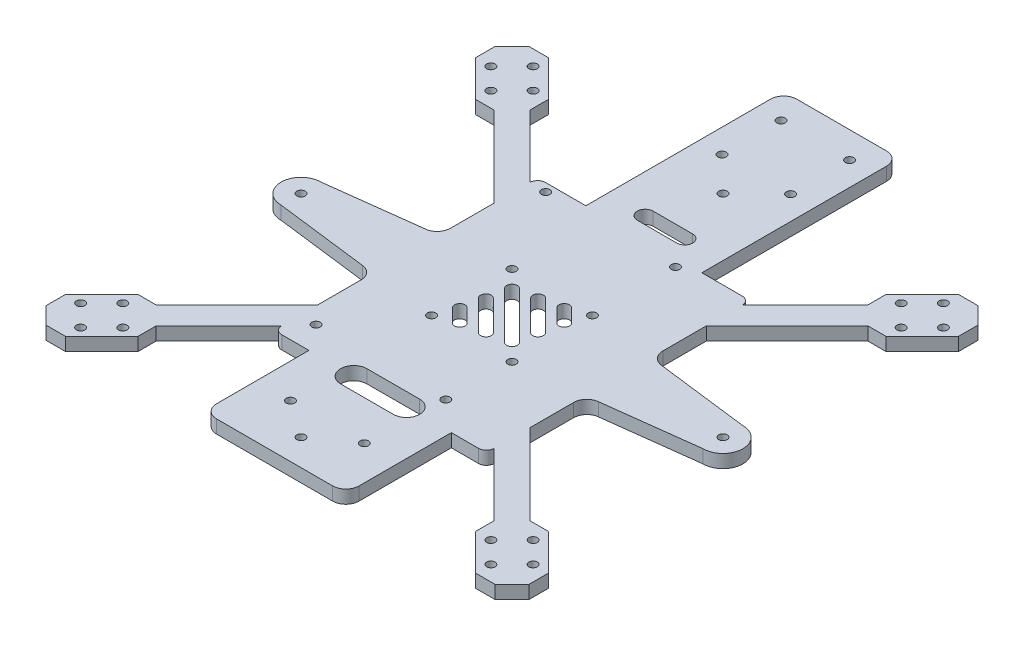
SolidWorks part; units mm, degrees
material "3k碳纤维板"
ref_plane "前视基准面" through (0, 0, 0) normal (0, 0, 1) x (1, 0, 0)
ref_plane "上视基准面" through (0, 0, 0) normal (0, 1, 0) x (1, 0, 0)
ref_plane "右视基准面" through (0, 0, 0) normal (1, 0, 0) x (0, 0, -1)
other "Configuration Table"
sketch "草图1" plane through (0, 0, 0) normal (0, 1, 0) x (1, 0, 0)
  line L0 (-40.28, 0) -> (40.28, 0) construction
  line L1 (-40.28, -50) -> (40.28, -50)
  line L2 (-40.28, -50) -> (-40.28, -16.9164)
  line L3 (-40.28, 50) -> (40.28, 50)
  line L4 (40.28, -50) -> (40.28, -16.9164)
  line L5 (-40.28, -50) -> (40.28, 50) construction
  line L6 (-40.28, 50) -> (40.28, -50) construction
  line L7 (0, -50) -> (0, 50) construction
  line L8 (-40.28, -50) -> (-40.28, -90) construction
  line L9 (-40.28, -90) -> (40.28, -90) construction
  line L10 (40.28, -90) -> (40.28, -50) construction
  line L11 (0, -50) -> (0, -90) construction
  line L12 (-40.28, -70) -> (40.28, -70) construction
  line L13 (-27, -90) -> (27, -90)
  line L14 (27, -90) -> (27, -50)
  line L15 (-27, -90) -> (-27, -50)
  line L16 (44.6626, 11.9547) -> (80, 7.5578)
  line L17 (44.6626, -11.9547) -> (80, -7.5578)
  line L18 (-44.6626, -11.9547) -> (-80, -7.5578)
  line L19 (-44.6626, 11.9547) -> (-80, 7.5578)
  line L20 (40.28, 16.9164) -> (40.28, 50)
  line L21 (-40.28, 16.9164) -> (-40.28, 50)
  circle A0 centre (-34.12, 46.89) radius 1.6
  circle A1 centre (15.09, 46.89) radius 1.6
  circle A2 centre (15.09, -40.19) radius 1.6
  circle A3 centre (-34.12, -40.19) radius 1.6
  circle A5 centre (-15.25, 15.25) radius 1.6
  circle A6 centre (15.25, 15.25) radius 1.6
  circle A7 centre (15.25, -15.25) radius 1.6
  circle A8 centre (-15.25, -15.25) radius 1.6
  circle A9 centre (14, -70) radius 1.6
  circle A10 centre (-14, -70) radius 1.6
  circle A11 centre (80, 0) radius 7.5 construction
  circle A12 centre (-80, 0) radius 7.5 construction
  circle A14 centre (80, 0) radius 1.6
  circle A16 centre (-80, 0) radius 1.6
  arc A17 (80, 7.5578) -> (80, -7.5578) centre (80, 0) cw
  arc A18 (-80, 7.5578) -> (-80, -7.5578) centre (-80, 0) ccw
  arc A19 (44.6626, 11.9547) -> (40.28, 16.9164) centre (45.28, 16.9164) cw
  arc A20 (44.6626, -11.9547) -> (40.28, -16.9164) centre (45.28, -16.9164) ccw
  arc A21 (-44.6626, -11.9547) -> (-40.28, -16.9164) centre (-45.28, -16.9164) cw
  arc A22 (-44.6626, 11.9547) -> (-40.28, 16.9164) centre (-45.28, 16.9164) ccw
  point P0 (0, 0)
  point P19 (0, 0)
  point P22 (0, 0)
  point P40 (0, -90)
  point P62 (40.28, 12.5)
  point P65 (40.28, -12.5)
  point P68 (-40.28, -12.5)
  point P71 (-40.28, 12.5)
  dimension "D3" = 3.2
  dimension "D10" = 3.2
  dimension "D11" = 30.5
  dimension "D12" = 30.5
  dimension "D14" = 3.2
  dimension "D18" = 15
  dimension "D21" = 3.2
  dimension "D19" = 160
  dimension "D23" = 5
  dimension "D1" = 80.56
  dimension "D2" = 100
  dimension "D4" = 6.16
  dimension "D5" = 3.11
  dimension "D8" = 49.21
  dimension "D9" = 87.08
  dimension "D13" = 40
  dimension "D15" = 28
  dimension "D16" = 54
  dimension "D17" = 25
  dimension "D6" = 2
  dimension "D7" = 2
extrude "凸台-拉伸1" add sketch "草图1" along normal blind 5 contours L15 L13 L14 L1 A9 A10 | L1 L4 L3 L2 A6 A5 A3 A2 A1 A0 A7 A8 region at (0.0313, 0, 0.011) region at (0, 0, 70)
sketch "草图6" plane through (0, 0, 0) normal (0, 1, 0) x (1, 0, 0)
  line L0 (0, 0) -> (50000, 0) construction
  line L1 (0, 0) -> (0, 50000) construction
  line L2 (-77.7817, 77.7817) -> (77.7817, 77.7817) construction
  line L3 (77.7817, 77.7817) -> (77.7817, -77.7817) construction
  line L4 (69.7817, 77.7817) -> (85.7817, 77.7817) construction
  line L5 (77.7817, 69.7817) -> (77.7817, 85.7817) construction
  line L6 (-77.7817, -77.7817) -> (77.7817, 77.7817) construction
  line L7 (77.7817, 91.5317) -> (64.0317, 77.7817)
  line L8 (91.5317, 77.7817) -> (77.7817, 64.0317)
  line L9 (-70.9067, 64.0317) -> (-40.28, 33.405)
  line L10 (-91.5317, -91.5317) -> (88.3498, 88.3498) construction
  line L11 (-87.5951, 87.5951) -> (77.7817, -77.7817) construction
  line L12 (40.28, -50) -> (40.28, 50)
  line L13 (40.28, 50) -> (-40.28, 50)
  line L14 (-40.28, 50) -> (-40.28, -50)
  line L15 (-40.28, -50) -> (40.28, -50)
  line L16 (-77.7817, 64.0317) -> (-70.9067, 64.0317)
  line L17 (-91.5317, 77.7817) -> (-77.7817, 64.0317)
  line L18 (-91.5317, 77.7817) -> (-91.5317, 85.1678)
  line L19 (-85.1678, 91.5317) -> (-91.5317, 85.1678)
  line L20 (-77.7817, 91.5317) -> (-85.1678, 91.5317)
  line L21 (77.7817, 91.5317) -> (85.1678, 91.5317)
  line L22 (91.5317, 77.7817) -> (91.5317, 85.1678)
  line L23 (-77.7817, 91.5317) -> (-64.0317, 77.7817)
  line L24 (-64.0317, 77.7817) -> (-64.0317, 70.9067)
  line L25 (72.1249, 83.4386) -> (83.4386, 72.1249) construction
  line L26 (77.7817, 64.0317) -> (70.9067, 64.0317)
  line L27 (64.0317, 77.7817) -> (64.0317, 70.9067)
  line L28 (77.7817, 64.0317) -> (70.9067, 64.0317)
  line L29 (64.0317, 77.7817) -> (64.0317, 70.9067)
  line L30 (64.0317, 70.9067) -> (40.28, 47.155)
  line L31 (70.9067, 64.0317) -> (40.28, 33.405)
  line L32 (85.1678, 91.5317) -> (91.5317, 85.1678)
  line L33 (-64.0317, 70.9067) -> (-40.28, 47.155)
  line L34 (-64.0317, -70.9067) -> (-40.28, -47.155)
  line L35 (-64.0317, -77.7817) -> (-64.0317, -70.9067)
  line L36 (-77.7817, -91.5317) -> (-64.0317, -77.7817)
  line L37 (-77.7817, -91.5317) -> (-85.1678, -91.5317)
  line L38 (-85.1678, -91.5317) -> (-91.5317, -85.1678)
  line L39 (-91.5317, -77.7817) -> (-91.5317, -85.1678)
  line L40 (-91.5317, -77.7817) -> (-77.7817, -64.0317)
  line L41 (-77.7817, -64.0317) -> (-70.9067, -64.0317)
  line L42 (-70.9067, -64.0317) -> (-40.28, -33.405)
  line L43 (70.9067, -64.0317) -> (40.28, -33.405)
  line L44 (77.7817, -64.0317) -> (70.9067, -64.0317)
  line L45 (91.5317, -77.7817) -> (77.7817, -64.0317)
  line L46 (91.5317, -77.7817) -> (91.5317, -85.1678)
  line L47 (85.1678, -91.5317) -> (91.5317, -85.1678)
  line L48 (77.7817, -91.5317) -> (85.1678, -91.5317)
  line L49 (77.7817, -91.5317) -> (64.0317, -77.7817)
  line L50 (64.0317, -77.7817) -> (64.0317, -70.9067)
  line L51 (64.0317, -70.9067) -> (40.28, -47.155)
  circle A0 centre (-77.7817, 77.7817) radius 65.9 construction
  circle A1 centre (77.7817, 77.7817) radius 65.9 construction
  circle A2 centre (-77.7817, -77.7817) radius 65.9 construction
  circle A3 centre (77.7817, -77.7817) radius 65.9 construction
  circle A4 centre (0, 0) radius 110 construction
  circle A5 centre (77.7817, 77.7817) radius 8 construction
  circle A6 centre (77.7817, 85.7817) radius 1.6
  circle A7 centre (85.7817, 77.7817) radius 1.6
  circle A8 centre (77.7817, 69.7817) radius 1.6
  circle A9 centre (69.7817, 77.7817) radius 1.6
  circle A10 centre (77.7817, 77.7817) radius 13.75 construction
  circle A11 centre (-77.7817, 85.7817) radius 1.6
  circle A12 centre (-85.7817, 77.7817) radius 1.6
  circle A13 centre (-69.7817, 77.7817) radius 1.6
  circle A14 centre (-77.7817, 69.7817) radius 1.6
  circle A15 centre (-77.7817, -69.7817) radius 1.6
  circle A16 centre (-69.7817, -77.7817) radius 1.6
  circle A17 centre (-85.7817, -77.7817) radius 1.6
  circle A18 centre (-77.7817, -85.7817) radius 1.6
  circle A19 centre (77.7817, -85.7817) radius 1.6
  circle A20 centre (85.7817, -77.7817) radius 1.6
  circle A21 centre (69.7817, -77.7817) radius 1.6
  circle A22 centre (77.7817, -69.7817) radius 1.6
  point P18 (77.7817, 77.7817)
  point P21 (77.7817, 77.7817)
  point P24 (0, 0)
  point P31 (77.7817, 77.7817)
  point P77 (77.7817, 77.7817)
  dimension "D1" = 3.2
  dimension "D2" = 3.2
  dimension "D3" = 3.2
  dimension "D4" = 3.2
  dimension "D5" = 3.2
  dimension "D6" = 3.2
  dimension "D7" = 3.2
  dimension "D8" = 3.2
  dimension "D9" = 3.2
  dimension "D10" = 3.2
  dimension "D11" = 3.2
  dimension "D12" = 3.2
  dimension "D13" = 3.2
  dimension "D14" = 3.2
  dimension "D15" = 3.2
  dimension "D16" = 3.2
extrude "凸台-拉伸3" add sketch "草图6" along normal blind 5 contours L33 L24 L23 L20 L19 L18 L17 L16 L9 L14 A13 A11 A12 A14 | L32 L21 L7 L27 L30 L12 L31 L26 L8 L22 A9 A8 A7 A6 | L51 L50 L49 L48 L47 L46 L45 L44 L43 L12 A21 A19 A20 A22 | L42 L41 L40 L39 L38 L37 L36 L35 L34 L14 A18 A17 A16 A15 region at (67.5211, 0, -67.3959) region at (67.5211, 0, 67.3959) region at (-67.5211, 0, -67.3959) region at (-67.5211, 0, 67.3959)
sketch "草图7" plane through (0, 0, 0) normal (0, 1, 0) x (1, 0, 0)
  line L0 (-8.8388, 8.8388) -> (8.8388, -8.8388) construction
  line L1 (-15.25, -15.25) -> (15.25, -15.25) construction
  line L2 (-15.25, -15.25) -> (-15.25, 15.25) construction
  line L3 (-15.25, 15.25) -> (15.25, 15.25) construction
  line L4 (15.25, -15.25) -> (15.25, 15.25) construction
  line L5 (-15.25, -15.25) -> (15.25, 15.25) construction
  line L6 (-15.25, 15.25) -> (15.25, -15.25) construction
  line L7 (-7.4246, 10.253) -> (10.253, -7.4246)
  line L8 (-10.253, 7.4246) -> (7.4246, -10.253)
  line L9 (-0.7071, 10.6066) -> (10.6066, -0.7071) construction
  line L10 (0.7071, 12.0208) -> (12.0208, 0.7071)
  line L11 (-2.1213, 9.1924) -> (9.1924, -2.1213)
  line L12 (7.4246, 12.3744) -> (12.3744, 7.4246) construction
  line L13 (8.8388, 13.7886) -> (13.7886, 8.8388)
  line L14 (6.0104, 10.9602) -> (10.9602, 6.0104)
  line L15 (-12.3744, -7.4246) -> (-7.4246, -12.3744) construction
  line L16 (-13.7886, -8.8388) -> (-8.8388, -13.7886)
  line L17 (-10.9602, -6.0104) -> (-6.0104, -10.9602)
  line L18 (-10.6066, 0.7071) -> (0.7071, -10.6066) construction
  line L19 (-12.0208, -0.7071) -> (-0.7071, -12.0208)
  line L20 (-9.1924, 2.1213) -> (2.1213, -9.1924)
  line L21 (0, -50) -> (0, 50) construction
  line L22 (-40.28, 50) -> (40.28, 50) construction
  line L23 (-27, -50) -> (27, -50) construction
  line L24 (-10, -50) -> (10, -50) construction
  line L25 (-10, -45) -> (10, -45)
  line L26 (-10, -55) -> (10, -55)
  arc A0 (-7.4246, 10.253) -> (-10.253, 7.4246) centre (-8.8388, 8.8388) ccw
  arc A1 (7.4246, -10.253) -> (10.253, -7.4246) centre (8.8388, -8.8388) ccw
  arc A2 (0.7071, 12.0208) -> (-2.1213, 9.1924) centre (-0.7071, 10.6066) ccw
  arc A3 (9.1924, -2.1213) -> (12.0208, 0.7071) centre (10.6066, -0.7071) ccw
  arc A4 (8.8388, 13.7886) -> (6.0104, 10.9602) centre (7.4246, 12.3744) ccw
  arc A5 (10.9602, 6.0104) -> (13.7886, 8.8388) centre (12.3744, 7.4246) ccw
  arc A6 (-13.7886, -8.8388) -> (-10.9602, -6.0104) centre (-12.3744, -7.4246) cw
  arc A7 (-6.0104, -10.9602) -> (-8.8388, -13.7886) centre (-7.4246, -12.3744) cw
  arc A8 (-12.0208, -0.7071) -> (-9.1924, 2.1213) centre (-10.6066, 0.7071) cw
  arc A9 (2.1213, -9.1924) -> (-0.7071, -12.0208) centre (0.7071, -10.6066) cw
  arc A10 (-10, -45) -> (-10, -55) centre (-10, -50) ccw
  arc A11 (10, -55) -> (10, -45) centre (10, -50) ccw
  circle A12 centre (0, -80) radius 1.6
  point P0 (0, 0)
  point P9 (0, 0)
  point P16 (4.9497, 4.9497)
  point P21 (9.8995, 9.8995)
  point P31 (-9.8995, -9.8995)
  point P38 (-4.9497, -4.9497)
  point P48 (0, 0)
  point P51 (0, -50)
  point P53 (0, -50)
  dimension "D3" = 4
  dimension "D7" = 2
  dimension "D9" = 5
  dimension "D11" = 3.2
  dimension "D1" = 4
  dimension "D2" = 25
  dimension "D4" = 3
  dimension "D5" = 16
  dimension "D6" = 7
  dimension "D8" = 3
  dimension "D10" = 20
  dimension "D12" = 80
extrude "切除-拉伸5" cut sketch "草图7" along normal through all contours A7 L17 A6 L16 | A9 L20 A8 L19 | L8 A1 L7 A0 | L11 A3 L10 A2 | L14 A5 L13 A4 | L26 A11 L25 A10 | A12 region at (0, 0, 0) region at (4.9497, 0, -4.9497) region at (9.8995, 0, -9.8995) region at (-9.8995, 0, 9.8995) region at (-4.9497, 0, 4.9497) region at (0, 0, 50) region at (0, 0, 80)
sketch "草图8" plane through (0, 0, 0) normal (0, 1, 0) x (1, 0, 0)
  line L0 (0, 0) -> (0, 87.5) construction
  line L1 (-40.28, 50) -> (40.28, 50) construction
  line L2 (-22, 125) -> (22, 125)
  line L3 (-22, 125) -> (-22, 50)
  line L4 (-22, 50) -> (22, 50)
  line L5 (22, 125) -> (22, 50)
  line L6 (-22, 125) -> (22, 50) construction
  line L7 (-22, 50) -> (22, 125) construction
  line L8 (13, 50) -> (13, 125) construction
  line L9 (-7.5, 58) -> (7.5, 58) construction
  line L10 (-7.5, 61) -> (7.5, 61)
  line L11 (-7.5, 55) -> (7.5, 55)
  circle A0 centre (13, 115) radius 1.6
  circle A1 centre (-13, 115) radius 1.6
  circle A2 centre (13, 92.63) radius 1.6
  circle A3 centre (-13, 92.63) radius 1.6
  arc A4 (-7.5, 61) -> (-7.5, 55) centre (-7.5, 58) ccw
  arc A5 (7.5, 55) -> (7.5, 61) centre (7.5, 58) ccw
  circle A6 centre (0, 80) radius 1.6
  point P21 (0, 58)
  dimension "D4" = 3.2
  dimension "D6" = 3.2
  dimension "D9" = 3
  dimension "D11" = 3.2
  dimension "D12" = 80
  dimension "D1" = 75
  dimension "D2" = 44
  dimension "D3" = 9
  dimension "D5" = 10
  dimension "D7" = 22.37
  dimension "D8" = 15
  dimension "D10" = 5
extrude "凸台-拉伸4" add sketch "草图8" along normal blind 5
fillet "圆角1" radius 5 4 edges at (-22, 2.5, -125) (22, 2.5, -125) (27, 2.5, 90) (-27, 2.5, 90)
fillet "圆角2" radius 3 4 edges at (-40.28, 2.5, 50) (40.28, 2.5, 50) (40.28, 2.5, -50) (-40.28, 2.5, -50)
